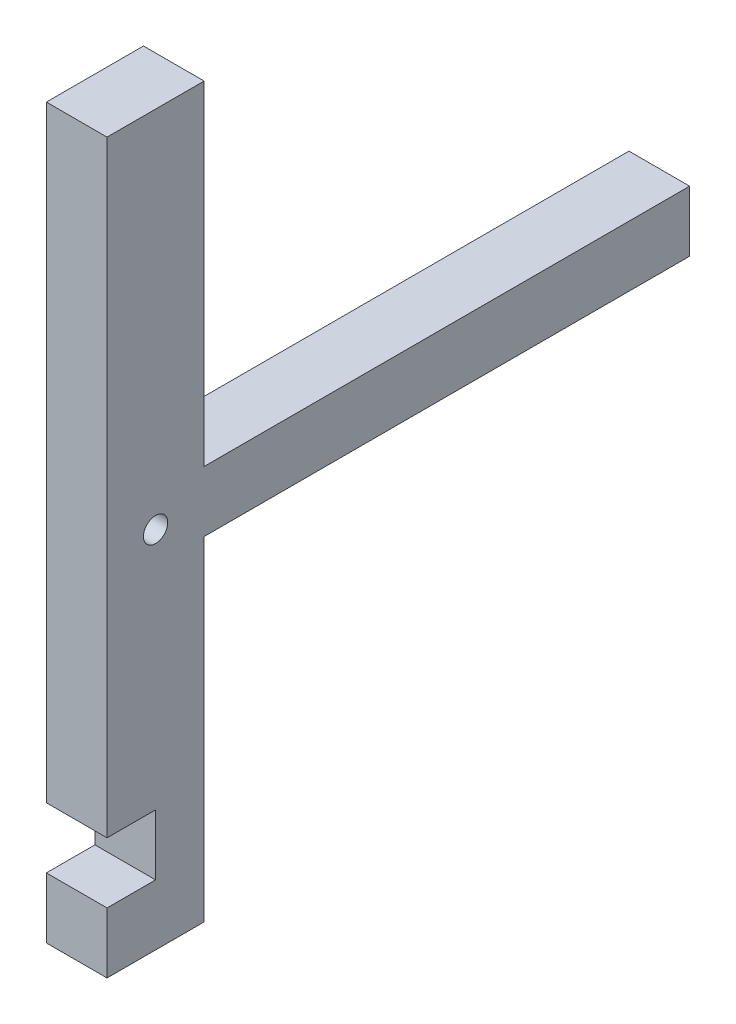
SolidWorks part; units mm, degrees
ref_plane "Front Plane" through (0, 0, 0) normal (0, 0, 1) x (1, 0, 0)
ref_plane "Top Plane" through (0, 0, 0) normal (0, 1, 0) x (1, 0, 0)
ref_plane "Right Plane" through (0, 0, 0) normal (1, 0, 0) x (0, 0, -1)
sketch "Elevator Paddle" plane through (0, 0, 0) normal (1, 0, 0) x (0, 0, -1)
  line L0 (-5.08, 0) -> (55.4696, 0) construction
  line L1 (-5.08, -38.1) -> (5.08, -38.1)
  line L2 (-5.08, -38.1) -> (-5.08, -31.75)
  line L3 (-5.08, 38.1) -> (5.08, 38.1)
  line L4 (5.08, -38.1) -> (5.08, -3.175)
  line L5 (-5.08, -38.1) -> (5.08, 38.1) construction
  line L6 (-5.08, 38.1) -> (5.08, -38.1) construction
  line L7 (5.08, -3.175) -> (55.88, -3.175)
  line L9 (5.08, 3.175) -> (55.88, 3.175)
  line L10 (55.88, -3.175) -> (55.88, 3.175)
  line L11 (0, 38.1) -> (0, -38.1) construction
  line L12 (-5.08, -31.75) -> (0, -31.75)
  line L13 (5.08, 3.175) -> (5.08, 38.1)
  line L14 (-5.08, -25.4) -> (0, -25.4)
  line L15 (0, -31.75) -> (0, -25.4)
  line L16 (-5.08, -25.4) -> (-5.08, 38.1)
  circle A0 centre (0, 0) radius 1.27
  point P0 (0, 0)
  point P14 (55.88, 0)
  dimension "D3" = 2.54
  dimension "D1" = 76.2
  dimension "D2" = 10.16
  dimension "D4" = 6.35
  dimension "D5" = 50.8
  dimension "D6" = 6.35
  dimension "D7" = 6.35
extrude "Boss-Extrude1" add sketch "Elevator Paddle" along normal blind 6.35 contours L16 L14 L15 L12 L2 L1 L4 L7 L10 L9 L13 L3 A0 region at (0, 0.8701, -9.3579)
equation "\"Ball Diameter\"= 1.75in"
equation "\"Sheet Thickness\"= 0.25in"
equation "\"Screw Diameter\"= .17in"
equation "\"Robot Diameter\"= 16in"
equation "\"Castor Screw Diameter\"= 0.22in"
equation "\"Wheel Diameter\"= 4in"
equation "\"Nut Diameter\"= 8.4mm"
equation "\"Nut Height\"= 2.9mm"
equation "\"Screw Height\"= 0.55in"
equation "\"D4@Elevator Paddle\"=\"Sheet Thickness\""
equation "\"D5@Elevator Paddle\"=\"Ball Diameter\"+0.25in"
equation "\"D6@Elevator Paddle\"=\"Sheet Thickness\""
equation "\"D7@Elevator Paddle\"=\"Sheet Thickness\""
equation "\"D1@Boss-Extrude1\"=\"Sheet Thickness\""
